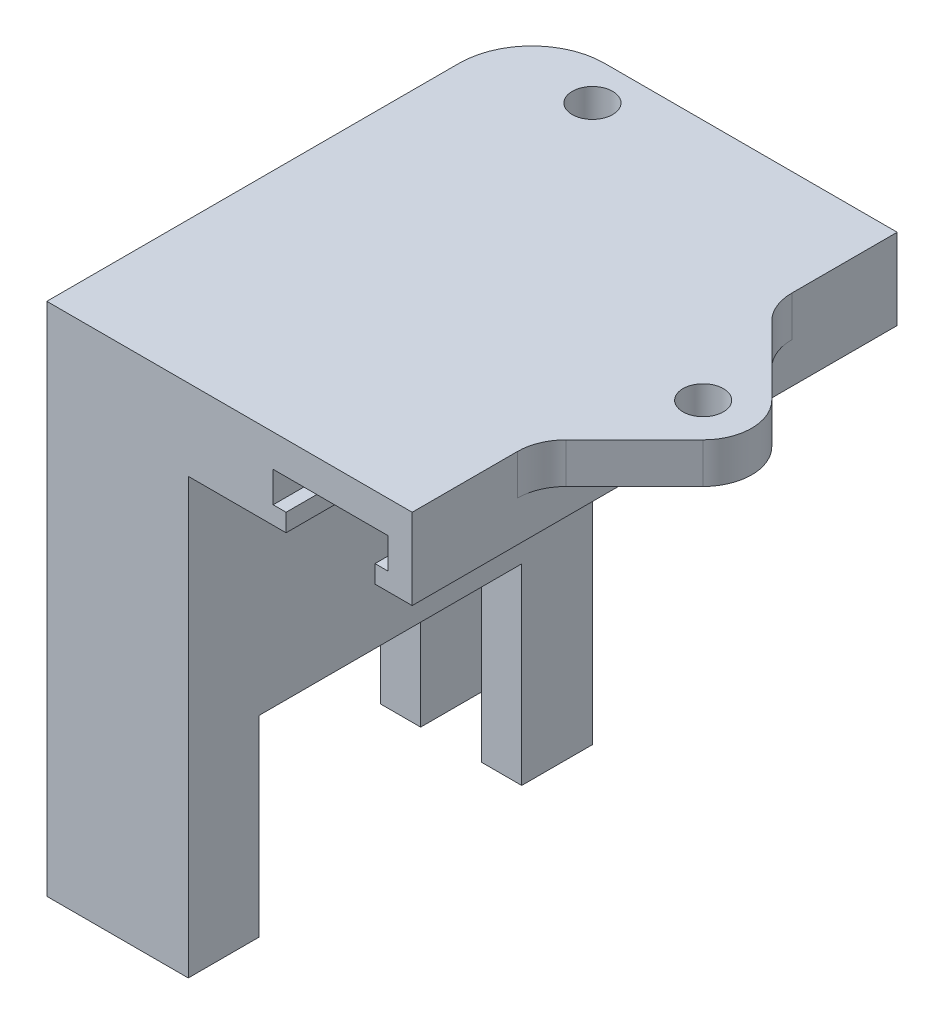
SolidWorks part; units mm, degrees
ref_plane "Front Plane" through (0, 0, 0) normal (0, 0, 1) x (1, 0, 0)
ref_plane "Top Plane" through (0, 0, 0) normal (0, 1, 0) x (1, 0, 0)
ref_plane "Right Plane" through (0, 0, 0) normal (1, 0, 0) x (0, 0, -1)
sketch "Sketch1" plane through (0, 0, 0) normal (0, 0, 1) x (1, 0, 0)
  line L0 (-12.827, 0) -> (12.827, 0)
  line L1 (12.827, 0) -> (12.827, -12.7)
  line L2 (12.827, -12.7) -> (6.985, -12.7)
  line L3 (6.985, -12.7) -> (6.985, -9.906)
  line L4 (6.985, -9.906) -> (9.017, -9.906)
  line L5 (9.017, -9.906) -> (9.017, -5.08)
  line L6 (9.017, -5.08) -> (-9.017, -5.08)
  line L7 (0, 0) -> (0, -5.08) construction
  line L8 (-9.017, -9.906) -> (-9.017, -5.08)
  line L9 (-6.985, -9.906) -> (-9.017, -9.906)
  line L10 (-6.985, -12.7) -> (-6.985, -9.906)
  line L11 (-12.827, -12.7) -> (-6.985, -12.7)
  line L12 (-12.827, 0) -> (-12.827, -12.7)
  dimension "D1" = 2.794
  dimension "D2" = 13.97
  dimension "D3" = 18.034
  dimension "D4" = 7.62
  dimension "D5" = 12.7
  dimension "D6" = 3.81
extrude "Boss-Extrude1" add sketch "Sketch1" along normal mid plane 76.2
sketch "Sketch2" plane through (0, 0, 0) normal (1, 0, 0) x (0, 0, -1)
  line L0 (-38.1, -5.08) -> (38.1, -5.08) construction
  line L1 (-38.1, -5.08) -> (38.1, -5.08) construction
  line L2 (6.858, -5.08) -> (9.398, -8.89)
  line L3 (9.398, -8.89) -> (11.938, -5.08)
  line L4 (11.938, -5.08) -> (6.858, -5.08)
  line L5 (9.398, -8.89) -> (9.398, -5.08) construction
  dimension "D1" = 3.81
  dimension "D2" = 5.08
  dimension "D3" = 47.498
extrude "Boss-Extrude2" add sketch "Sketch2" along normal mid plane 2.54 contours L3 L4 L2
sketch "Sketch3" plane through (0, 0, 0) normal (0, 1, 0) x (1, 0, 0)
  line L0 (12.827, 0) -> (28.067, 0) construction
  line L1 (12.827, -38.1) -> (12.827, 38.1) construction
  line L2 (0, 38.1) -> (0, -38.1) construction
  line L3 (12.827, 38.1) -> (-12.827, 38.1) construction
  line L4 (12.827, -38.1) -> (-12.827, -38.1) construction
  line L5 (15.0588, 16.1645) -> (25.8352, 5.3882)
  line L6 (12.827, 21.5526) -> (12.827, -21.5526)
  line L7 (12.827, 21.5526) -> (12.827, 38.1) construction
  line L8 (12.827, -21.5526) -> (12.827, -38.1) construction
  line L9 (15.0588, -16.1645) -> (25.8352, -5.3882)
  arc A0 (25.8352, -5.3882) -> (25.8352, 5.3882) centre (20.447, 0) ccw
  arc A1 (15.0588, 16.1645) -> (12.827, 21.5526) centre (20.447, 21.5526) cw
  circle A2 centre (20.447, 0) radius 3.175
  arc A3 (15.0588, -16.1645) -> (12.827, -21.5526) centre (20.447, -21.5526) ccw
  line M9 (-12.827, 38.1) -> (-12.827, -38.1)
  line M11 (12.827, -38.1) -> (12.827, 38.1)
  dimension "D1" = 7.62
  dimension "D2" = 6.35
  dimension "D3" = 7.62
  dimension "D4" = 7.62
  dimension "D5" = 45
extrude "Boss-Extrude3" add sketch "Sketch3" against normal blind 6.35 contours A3 L9 A0 L5 A1 A2 M11 | M9 region at (20.1237, 0, -10.453)
sketch "Sketch4" plane through (0, 0, 38.1) normal (0, 0, 1) x (1, 0, 0)
  line L0 (-12.827, 0) -> (-44.577, 0)
  line L1 (-44.577, 0) -> (-44.577, -50.8)
  line L2 (-44.577, -50.8) -> (-22.352, -50.8)
  line L3 (-22.352, -50.8) -> (-22.352, -12.7)
  line L4 (-22.352, -12.7) -> (-12.827, -12.7)
  line L5 (-12.827, 0) -> (-12.827, -12.7)
  dimension "D1" = 50.8
  dimension "D2" = 9.525
  dimension "D3" = 31.75
extrude "Boss-Extrude4" add sketch "Sketch4" against normal blind 63.5
sketch "Sketch5" plane through (-44.577, 0, 0) normal (-1, 0, 0) x (0, 0, 1)
  line L1 (-25.4, -50.8) -> (-14.2875, -50.8)
  line L2 (-25.4, -50.8) -> (-25.4, -80.9625)
  line L3 (-25.4, -80.9625) -> (-14.2875, -80.9625)
  line L4 (-14.2875, -50.8) -> (-14.2875, -80.9625)
  line L5 (38.1, -50.8) -> (26.9875, -50.8)
  line L6 (38.1, -50.8) -> (38.1, -80.9625)
  line L7 (38.1, -80.9625) -> (26.9875, -80.9625)
  line L8 (26.9875, -50.8) -> (26.9875, -80.9625)
  dimension "D1" = 41.275
  dimension "D2" = 30.1625
extrude "Boss-Extrude5" add sketch "Sketch5" against normal up to surface (22.225 mm away) up to face at (-22.352, -31.75, 6.35)
sketch "Sketch7" plane through (0, 0, -25.4) normal (0, 0, -1) x (-1, 0, 0)
  line L0 (22.352, -50.8) -> (44.577, -50.8) construction
  line L1 (22.352, -50.8) -> (44.577, -50.8) construction
  line L2 (22.352, -80.9625) -> (44.577, -80.9625) construction
  line L3 (38.227, -50.8) -> (28.702, -50.8)
  line L4 (38.227, -50.8) -> (38.227, -80.9625)
  line L5 (38.227, -80.9625) -> (28.702, -80.9625)
  line L6 (28.702, -50.8) -> (28.702, -80.9625)
  line L7 (33.4645, -50.8) -> (33.4645, -80.9625) construction
  dimension "D1" = 9.525
extrude "Cut-Extrude1" cut sketch "Sketch7" against normal up to next
sketch "Sketch8" plane through (0, 0, 0) normal (0, 1, 0) x (1, 0, 0)
  line L0 (-28.702, 38.1) -> (-28.702, 25.4) construction
  line L1 (-44.577, 25.4) -> (-12.827, 25.4)
  line L2 (-44.577, 25.4) -> (-44.577, 38.1)
  line L3 (-44.577, 38.1) -> (-12.827, 38.1)
  line L4 (-12.827, 25.4) -> (-12.827, 38.1)
  circle A0 centre (-28.702, 31.75) radius 3.175
  point P12 (0, 0)
  dimension "D1" = 6.35
extrude "Boss-Extrude6" add sketch "Sketch8" against normal blind 6.35
fillet "Fillet1" radius 11.43 1 edges at (-44.577, -3.175, -38.1)
